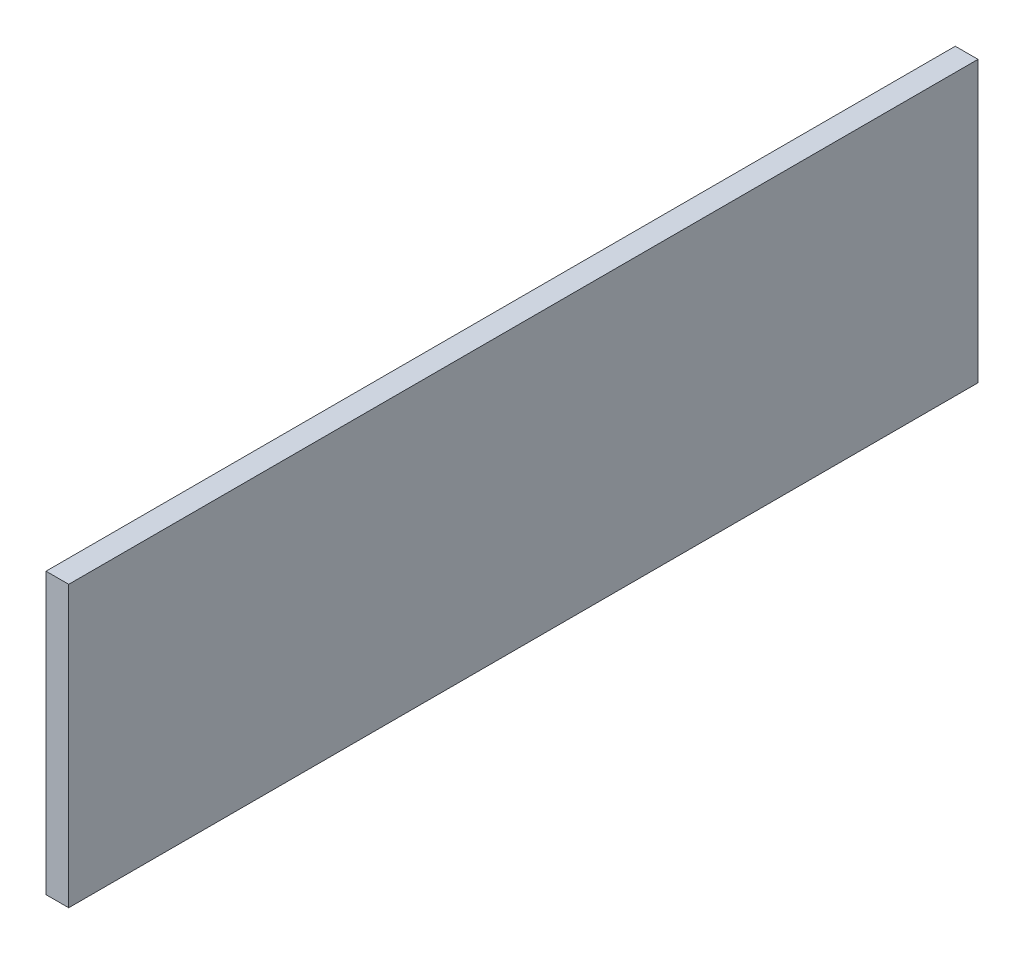
SolidWorks part; units mm, degrees
material "6061-T6 (SS)"
ref_plane "Front" through (0, 0, 0) normal (0, 0, 1) x (1, 0, 0)
ref_plane "Top" through (0, 0, 0) normal (0, 1, 0) x (1, 0, 0)
ref_plane "Right" through (0, 0, 0) normal (1, 0, 0) x (0, 0, -1)
sketch "Sketch1" plane through (0, 0, 0) normal (0, 0, 1) x (1, 0, 0)
  line L0 (-240.475, 9.525) -> (240.475, 9.525)
  line L1 (-250, 0) -> (250, 0)
  line L2 (-250, 0) -> (-250, 500)
  line L3 (-250, 500) -> (250, 500)
  line L4 (250, 0) -> (250, 500)
  line L5 (240.475, 9.525) -> (240.475, 490.475)
  line L6 (-240.475, 490.475) -> (240.475, 490.475)
  line L7 (-240.475, 9.525) -> (-240.475, 490.475)
  line L8 (-142.3043, 490.475) -> (-142.3043, 373.0167) construction
  line L9 (-240.475, 373.0167) -> (240.475, 373.0167)
  line L10 (-240.475, 373.0167) -> (-240.475, 363.4917)
  line L11 (-240.475, 363.4917) -> (240.475, 363.4917)
  line L12 (240.475, 373.0167) -> (240.475, 363.4917)
  line L13 (-240.475, 246.0333) -> (240.475, 246.0333)
  line L14 (-240.475, 246.0333) -> (-240.475, 236.5083)
  line L15 (-240.475, 236.5083) -> (240.475, 236.5083)
  line L16 (240.475, 246.0333) -> (240.475, 236.5083)
  line L17 (-240.475, 119.05) -> (240.475, 119.05)
  line L18 (-240.475, 119.05) -> (-240.475, 109.525)
  line L19 (-240.475, 109.525) -> (240.475, 109.525)
  line L20 (240.475, 119.05) -> (240.475, 109.525)
  line L21 (-142.3043, 363.4917) -> (-142.3043, 246.0333) construction
  line L22 (-142.3043, 236.5083) -> (-142.3043, 119.05) construction
  line L23 (-240.475, 431.7458) -> (-86.5083, 431.7458) construction
  line L24 (-86.5083, 490.475) -> (-76.9833, 490.475)
  line L25 (-86.5083, 490.475) -> (-86.5083, 373.0167)
  line L26 (-86.5083, 373.0167) -> (-76.9833, 373.0167)
  line L27 (-76.9833, 490.475) -> (-76.9833, 373.0167)
  line L28 (76.9833, 490.475) -> (86.5083, 490.475)
  line L29 (76.9833, 490.475) -> (76.9833, 373.0167)
  line L30 (76.9833, 373.0167) -> (86.5083, 373.0167)
  line L31 (86.5083, 490.475) -> (86.5083, 373.0167)
  line L32 (-76.9833, 431.7458) -> (76.9833, 431.7458) construction
  line L33 (86.5083, 431.7458) -> (240.475, 431.7458) construction
  line L34 (-131.311, 490.475) -> (-131.311, 363.4917) construction
  dimension "D1" = 500
  dimension "D2" = 9.525
  dimension "D3" = 9.525
  dimension "D4" = 100
  dimension "D5" = 9.525
  dimension "D6" = 117.4583
  dimension "D7" = 117.4583
  dimension "D8" = 126.9833
extrude "Boss-Extrude1" add sketch "Sketch1" along normal blind 381.25 contours L27 L6 L25 L9 region at (-81.7458, 431.7458, 0)
